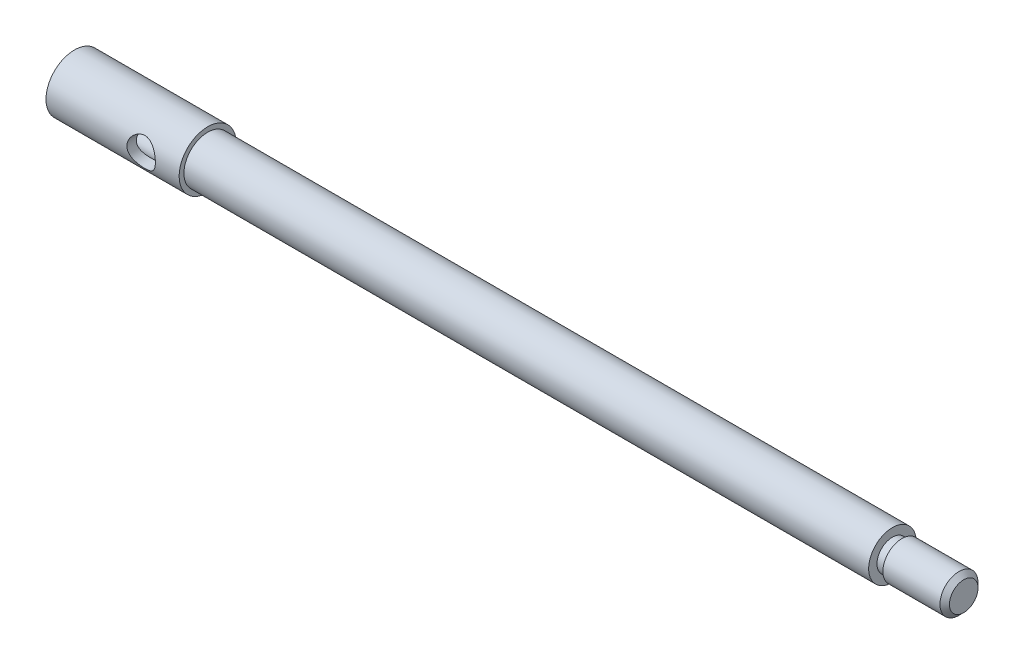
SolidWorks part; units mm, degrees
ref_plane "前视基准面" through (0, 0, 0) normal (0, 0, 1) x (1, 0, 0)
ref_plane "上视基准面" through (0, 0, 0) normal (0, 1, 0) x (1, 0, 0)
ref_plane "右视基准面" through (0, 0, 0) normal (1, 0, 0) x (0, 0, -1)
sketch "草图3" plane through (0, 0, 0) normal (1, 0, 0) x (0, 0, -1)
  circle A0 centre (0, 0) radius 4
  dimension "D1" = 8
extrude "凸台-拉伸1" add sketch "草图3" against normal blind 13
cosmetic thread "装饰螺纹线1" parameters "D2"=6.647
sketch "草图5" plane through (-13, 0, 0) normal (-1, 0, 0) x (0, 0, 1)
  circle A0 centre (0, 0) radius 3.25
  dimension "D1" = 6.5
extrude "凸台-拉伸2" add sketch "草图5" along normal blind 2
sketch "草图6" plane through (-15, 0, 0) normal (-1, 0, 0) x (0, 0, 1)
  circle A0 centre (0, 0) radius 5
  dimension "D1" = 10
extrude "凸台-拉伸3" add sketch "草图6" along normal blind 144
chamfer "倒角2" distance 1 angle 45 1 edges at (0, 0, -4)
sketch "草图69" plane through (-159, 0, 0) normal (-1, 0, 0) x (0, 0, 1)
  circle A0 centre (0, 0) radius 6
extrude "凸台-拉伸4" add sketch "草图69" along normal blind 28
sketch "草图70" plane through (0, 0, 0) normal (0, 0, 1) x (1, 0, 0)
  line L0 (-187, 6) -> (-187, -6) construction
  circle A0 centre (-167, 0) radius 3
  dimension "D1" = 20
  dimension "D2" = 6
hole_wizard "孔1" positions "草图71" profile "草图73" legacy
sketch "草图71" plane through (-187, 0, 0) normal (-1, 0, 0) x (0, 0, 1)
  point P0 (0, 0)
sketch "草图73" plane through (-187, 0, 0) normal (0, 1, 0) x (0, 0, 1)
  line L0 (0, 0) -> (0, 27.4034)
  line L1 (0, 27.4034) -> (4, 25)
  line L2 (4, 25) -> (4, 0)
  line L5 (4, 0) -> (0, 0)
  line L10 (0, 27.4034) -> (-4, 25) construction
  line L11 (0, -6.35) -> (0, 107.95) construction
  dimension "孔直径" = 8
  dimension "孔深度" = 25
  dimension "导头角度" = 118
extrude "切除-拉伸1" cut sketch "草图70" against normal blind 28 and the other way blind 28
